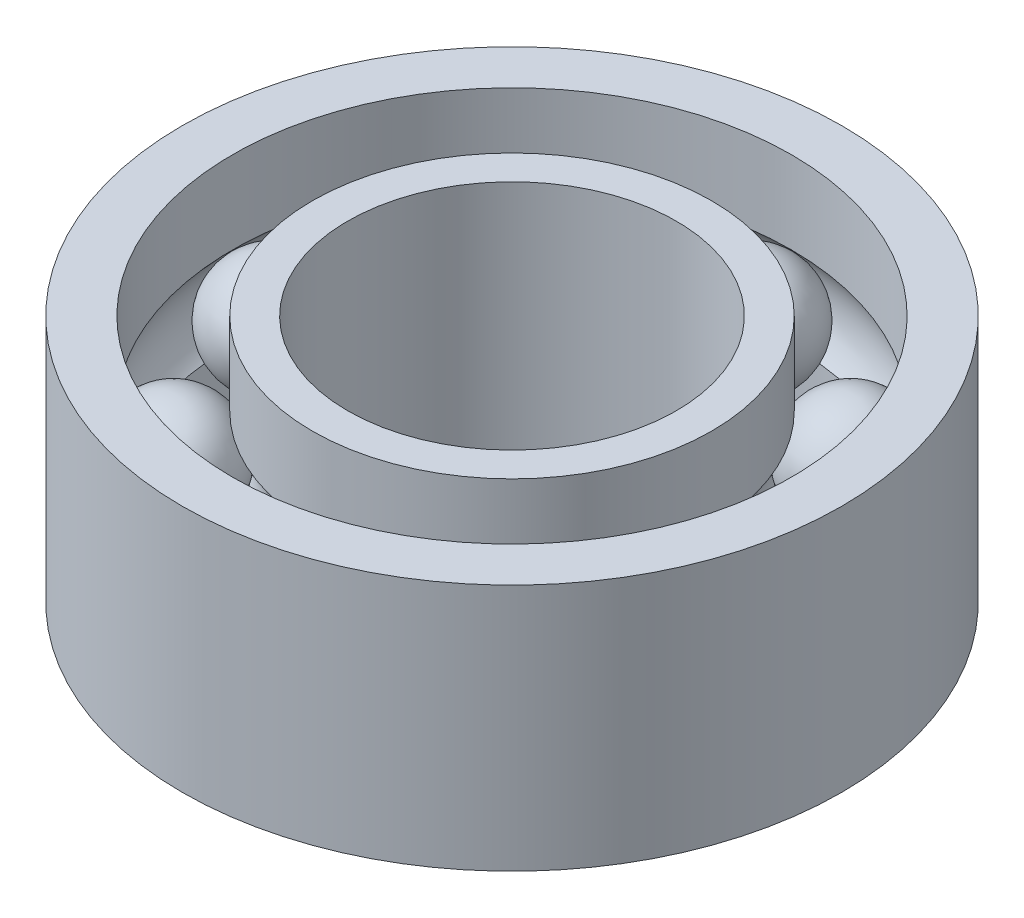
SolidWorks part; units mm, degrees
material "1060 合金"
ref_plane "前视基准面" through (0, 0, 0) normal (0, 0, 1) x (1, 0, 0)
ref_plane "上视基准面" through (0, 0, 0) normal (0, 1, 0) x (1, 0, 0)
ref_plane "右视基准面" through (0, 0, 0) normal (1, 0, 0) x (0, 0, -1)
sketch "草图1" plane through (0, 0, 0) normal (0, 1, 0) x (1, 0, 0)
  circle A0 centre (0, 0) radius 6.36
  circle A1 centre (0, 0) radius 5.39
  dimension "D1" = 12.72
  dimension "D2" = 10.78
extrude "凸台-拉伸1" add sketch "草图1" along normal blind 4.78
sketch "草图2" plane through (0, 0, 0) normal (0, 1, 0) x (1, 0, 0)
  circle A0 centre (0, 0) radius 3.85
  circle A1 centre (0, 0) radius 3.17
  dimension "D1" = 7.7
  dimension "D2" = 6.34
extrude "凸台-拉伸2" add sketch "草图2" along normal blind 4.78 separate body
ref_plane "基准面4" through (0, 2.39, 0) normal (0, 1, 0) x (1, 0, 0)
sketch "草图6" plane through (0, 0, 0) normal (0, 0, 1) x (1, 0, 0)
  line L0 (0, 4.78) -> (0, 0) construction
  line L3 (6.996, 2.39) -> (-6.996, 2.39) construction
  line L4 (-4.62, 3.49) -> (-4.62, 1.29)
  arc A0 (-4.62, 3.49) -> (-4.62, 1.29) centre (-4.62, 2.39) ccw
  circle A1 centre (-4.62, 2.39) radius 1.11
  dimension "D1" = 2.2
  dimension "D4" = 2.22
  dimension "D2" = 4.62
  dimension "D3" = 0
revolve "切除-旋转5" cut sketch "草图6" angle 360 about axis through (0, 4.78, 0) along (0, -1, 0)
revolve "旋转1" add sketch "草图6<3>" angle 360 about L4 region at (-5.0869, 2.39, 0)
sketch "草图6<3>" plane through (0, 0, 0) normal (0, 0, 1) x (1, 0, 0) same geometry as "草图6"
pattern_circular "阵列(圆周)2" count 8 over 360 about axis through (0, 4.78, 0) along (0, -1, 0) of bodies 128
